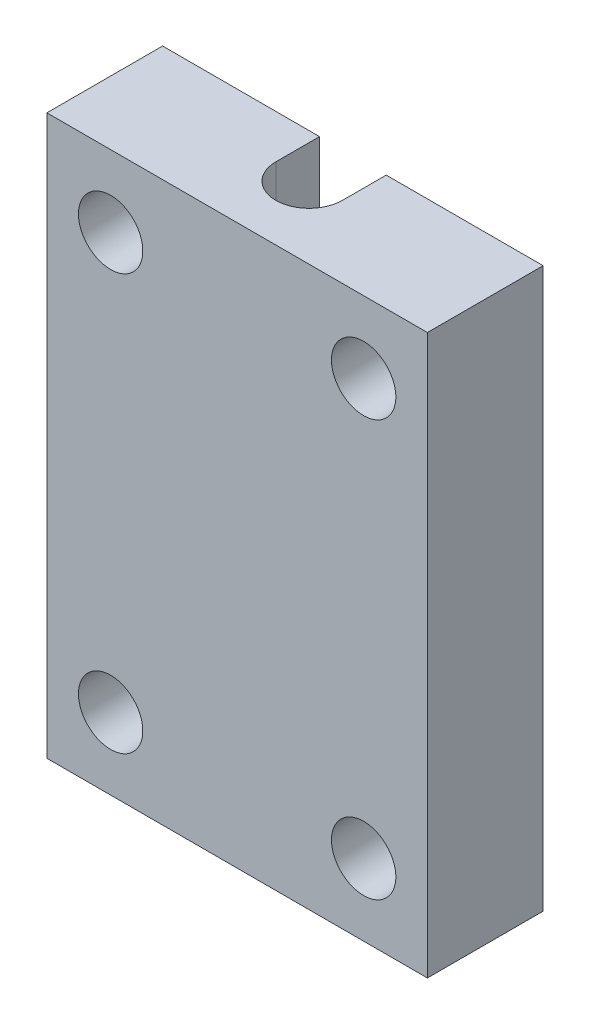
SolidWorks part; units mm, degrees
ref_plane "Front Plane" through (0, 0, 0) normal (0, 0, 1) x (1, 0, 0)
ref_plane "Top Plane" through (0, 0, 0) normal (0, 1, 0) x (1, 0, 0)
ref_plane "Right Plane" through (0, 0, 0) normal (1, 0, 0) x (0, 0, -1)
sketch "Sketch1" plane through (0, 0, 0) normal (0, 1, 0) x (1, 0, 0)
  line L0 (-9.7, 0) -> (-1.7, 0)
  line L1 (-9.7, 0) -> (-9.7, -5.9)
  line L2 (9.7, -5.9) -> (9.7, 0)
  line L19 (1.7, 0) -> (9.7, 0)
  line L21 (-1.7, -2.23) -> (-1.7, 0)
  line L27 (1.7, -2.23) -> (1.7, 0)
  line L28 (-9.7, -5.9) -> (9.7, -5.9)
  arc A2 (-1.7, -2.23) -> (1.7, -2.23) centre (0, -2.23) ccw
extrude "Boss-Extrude1" add sketch "Sketch1" along normal blind 28.5
sketch "Sketch2" plane through (0, 0, 0) normal (0, 0, -1) x (-1, 0, 0)
  circle A1 centre (6.45, 24.8442) radius 1.64
  circle A2 centre (6.45, 3.6558) radius 1.64
  circle A3 centre (-6.45, 3.6558) radius 1.64
  circle A4 centre (-6.45, 24.8442) radius 1.64
extrude "Cut-Extrude1" cut sketch "Sketch2" against normal up to surface (5.9 mm away) up to face at (0, 14.25, 5.9)
sketch "Sketch4" plane through (0, 0, 0) normal (0, 0, -1) x (-1, 0, 0)
  line L7 (1.7, 17.4013) -> (1.7, 16.3683)
  line L9 (-1.7, 17.4013) -> (-1.7, 16.3683)
  line L12 (1.7, 12.5317) -> (1.7, 11.4987)
  line L13 (-1.7, 12.5317) -> (-1.7, 11.4987)
  arc A0 (-1.7593, 16.2262) -> (-1.7593, 12.6738) centre (0, 14.45) ccw
  arc A2 (1.7593, 12.6738) -> (1.7593, 16.2262) centre (0, 14.45) ccw
  arc A5 (1.7593, 12.6738) -> (1.7, 12.5317) centre (1.9, 12.5317) ccw
  arc A7 (-1.7593, 12.6738) -> (-1.7, 12.5317) centre (-1.9, 12.5317) cw
  arc A8 (-1.7593, 16.2262) -> (-1.7, 16.3683) centre (-1.9, 16.3683) ccw
  arc A10 (1.7, 16.3683) -> (1.7593, 16.2262) centre (1.9, 16.3683) ccw
  arc A12 (-2.0083, 17.5695) -> (-2.0083, 11.3305) centre (0, 14.45) ccw
  arc A13 (2.0083, 11.3305) -> (2.0083, 17.5695) centre (0, 14.45) ccw
  arc A14 (2.0083, 11.3305) -> (1.7, 11.4987) centre (1.9, 11.4987) cw
  arc A15 (-2.0083, 11.3305) -> (-1.7, 11.4987) centre (-1.9, 11.4987) ccw
  arc A16 (-2.0083, 17.5695) -> (-1.7, 17.4013) centre (-1.9, 17.4013) cw
  arc A17 (1.7, 17.4013) -> (2.0083, 17.5695) centre (1.9, 17.4013) cw
extrude "Boss-Extrude2" add sketch "Sketch4" along normal blind 0.5
sketch "Sketch5" plane through (0, 0, -0.5) normal (0, 0, -1) x (-1, 0, 0)
  circle A0 centre (0, 14.45) radius 2.5
extrude "Cut-Extrude3" cut sketch "Sketch5" against normal blind 3.5
